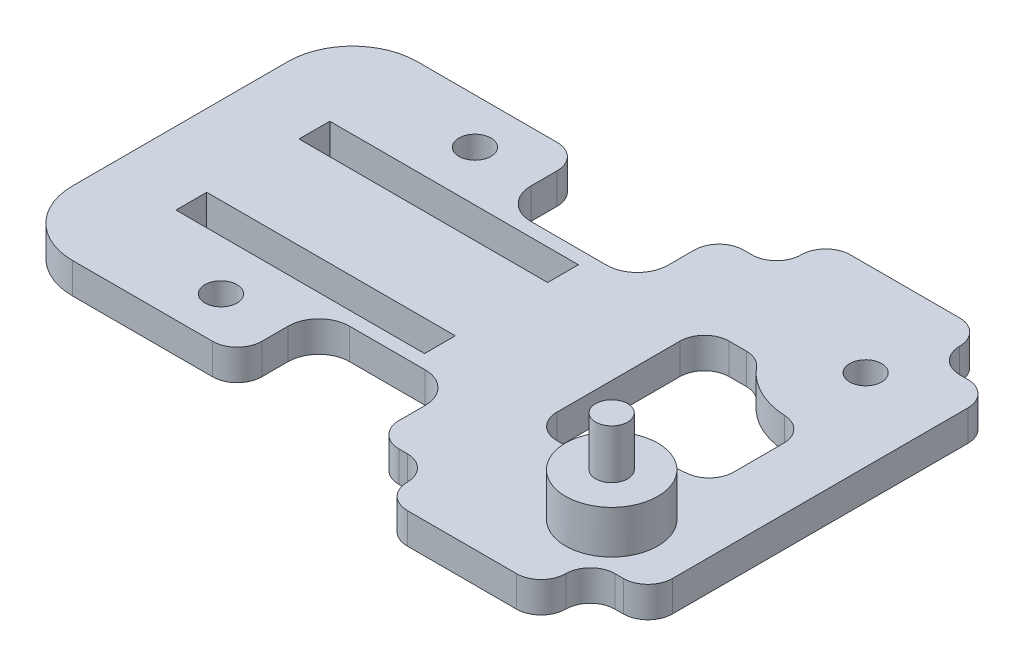
SolidWorks part; units mm, degrees
other "下垫片"
ref_plane "前视基准面" through (0, 0, 0) normal (0, 0, 1) x (1, 0, 0)
ref_plane "上视基准面" through (0, 0, 0) normal (0, 1, 0) x (1, 0, 0)
ref_plane "右视基准面" through (0, 0, 0) normal (1, 0, 0) x (0, 0, -1)
other "Configuration Table"
sketch "草图1" plane through (0, 0, 0) normal (0, 1, 0) x (1, 0, 0)
  line L0 (-89.3251, 0) -> (102.0425, 0) construction
  line L1 (0, 56.7239) -> (0, -62.578) construction
  line L2 (-47.2, -7.5) -> (-6.8, -7.5)
  line L3 (-47.2, 12.5) -> (-6.8, 12.5)
  line L4 (-47.2, 12.5) -> (-47.2, 7.5)
  line L5 (-47.2, 7.5) -> (-6.8, 7.5)
  line L6 (-6.8, 12.5) -> (-6.8, 7.5)
  line L7 (-47.2, 12.5) -> (-6.8, 7.5) construction
  line L8 (-47.2, 7.5) -> (-6.8, 12.5) construction
  line L9 (-6.8, -12.5) -> (-6.8, -7.5)
  line L10 (-47.2, -12.5) -> (-6.8, -12.5)
  line L11 (-47.2, -12.5) -> (-47.2, -7.5)
  line L14 (-21.75, -26.5375) -> (-21.75, -14.7375)
  line L15 (-21.75, -14.7375) -> (0.55, -14.7375)
  line L16 (0.55, -26.5375) -> (0.55, -14.7375)
  line L17 (-21.75, -26.5375) -> (0.55, -14.7375) construction
  line L18 (-21.75, -14.7375) -> (0.55, -26.5375) construction
  line L19 (-21.75, 14.7375) -> (0.55, 14.7375)
  line L20 (0.55, 26.5375) -> (0.55, 14.7375)
  line L22 (-21.75, 26.5375) -> (-21.75, 14.7375)
  line L23 (-21.75, 30.0095) -> (0.55, 30.0095)
  line L25 (-21.75, -26.5375) -> (-21.75, -30.0095)
  line L26 (-21.75, -30.0095) -> (0.55, -30.0095)
  line L27 (0.55, -26.5375) -> (0.55, -30.0095)
  line L28 (0.55, 26.5375) -> (0.55, 30.0095)
  line L30 (-21.75, 26.5375) -> (-21.75, 30.0095)
  circle A0 centre (-31.75, 20.6375) radius 2.6
  circle A4 centre (31.75, 20.6375) radius 2.6
  circle A5 centre (31.75, -20.6375) radius 2.6
  circle A6 centre (-31.75, -20.6375) radius 2.6
  point P13 (-27, 10)
  point P22 (-10.6, -20.6375)
  point P35 (-27, 10)
  dimension "D5" = 5.2
  dimension "D11" = 5.2
  dimension "D1" = 40.4
  dimension "D2" = 31.75
  dimension "D3" = 5
  dimension "D4" = 20.6375
  dimension "D6" = 10
  dimension "D7" = 22.3
  dimension "D8" = 11.8
  dimension "D9" = 0
  dimension "D10" = 31.2
  dimension "D12" = 5
  dimension "D13" = 40.4
  dimension "D14" = 27
  dimension "D15" = 10
  dimension "D16" = 2.2375
sketch "草图3" plane through (0, 0, 0) normal (0, 1, 0) x (1, 0, 0)
  line L0 (-40, 28) -> (-59, 28)
  line L1 (-40, -28) -> (9.9, -28)
  line L3 (-40, 28) -> (9.9, 28)
  line L5 (-40, -28) -> (40, 28) construction
  line L6 (-40, 28) -> (40, -28) construction
  line L7 (-59, 28) -> (-59, -28)
  line L8 (-59, -28) -> (-40, -28)
  line L10 (45, 28) -> (45, -28)
  line L15 (-45.7746, 0) -> (58.2399, 0) construction
  line L19 (9.9, 28) -> (9.9, 36)
  line L20 (9.9, 36) -> (35.65, 36)
  line L21 (35.65, 36) -> (35.65, 28)
  line L22 (35.65, 28) -> (45, 28)
  line L23 (35.65, -28) -> (45, -28)
  line L24 (35.65, -36) -> (35.65, -28)
  line L25 (9.9, -36) -> (35.65, -36)
  line L26 (9.9, -28) -> (9.9, -36)
  point P0 (0, 0)
  dimension "D1" = 56
  dimension "D2" = 80
  dimension "D3" = 19
  dimension "D4" = 5
  dimension "D5" = 9.35
  dimension "D6" = 8
  dimension "D7" = 25.75
extrude "凸台-拉伸1" add sketch "草图3" along normal blind 5
extrude "切除-拉伸1" cut sketch "草图1" along normal up to surface (5 mm away) up to face at (12.85, 5, 0)
sketch "草图5" plane through (0, 5, 0) normal (0, 1, 0) x (1, 0, 0)
  circle A0 centre (31.75, -20.6375) radius 7.5
  dimension "D1" = 15
extrude "凸台-拉伸2" add sketch "草图5" along normal blind 7
sketch "草图6" plane through (0, 12, 0) normal (0, 1, 0) x (1, 0, 0)
  circle A0 centre (31.75, -20.6375) radius 2.6
  dimension "D1" = 5.2
extrude "凸台-拉伸3" add sketch "草图6" along normal blind 8
fillet "圆角1" radius 5 4 edges at (0.55, 2.5, 14.7375) (-21.75, 2.5, 14.7375) (0.55, 2.5, -14.7375) (-21.75, 2.5, -14.7375)
fillet "圆角2" radius 4 14 edges at (0.55, 2.5, 28) (-21.75, 2.5, 28) (0.55, 2.5, -28) (-21.75, 2.5, -28) (9.9, 2.5, 28) (9.9, 2.5, 36) (35.65, 2.5, 36) (35.65, 2.5, 28) (45, 2.5, 28) (45, 2.5, -28) (35.65, 2.5, -28) (35.65, 2.5, -36) (9.9, 2.5, -36) (9.9, 2.5, -28)
sketch "草图7" plane through (0, 0, 0) normal (0, -1, 0) x (1, 0, 0)
  line L0 (-31.75, 20.6375) -> (31.75, 20.6375) construction
  line L1 (0, 27.9483) -> (0, -23.2551) construction
sketch "草图14" plane through (0, 5, 0) normal (0, 1, 0) x (1, 0, 0)
  line L0 (-11.6114, 0) -> (10.899, 0) construction
  line L1 (21.04, 14) -> (12.2, 14)
  line L2 (12.2, 14) -> (12.2, -14)
  line L3 (45, -24) -> (45, 24) construction
  line L4 (35, 8.4639) -> (35, -8.4639)
  line L5 (21.04, -14) -> (12.2, -14)
  arc A0 (35, 8.4639) -> (21.04, 14) centre (31.75, 20.6375) cw
  arc A1 (35, -8.4639) -> (21.04, -14) centre (31.75, -20.6375) ccw
  point P5 (35, 0)
  point P7 (21.04, 14)
  point P8 (35, 8.4639)
  point P18 (12.2, 0)
  dimension "D1" = 12.6
  dimension "D2" = 14
  dimension "D3" = 12.2
  dimension "D4" = 10
extrude "切除-拉伸6" cut sketch "草图14" against normal through all
fillet "圆角5" radius 4 6 edges at (35, 2.5, 8.4639) (21.04, 2.5, 14) (12.2, 2.5, 14) (21.04, 2.5, -14) (35, 2.5, -8.4639) (12.2, 2.5, -14)
fillet "圆角6" radius 10.5 2 edges at (-59, 2.5, 28) (-59, 2.5, -28)
